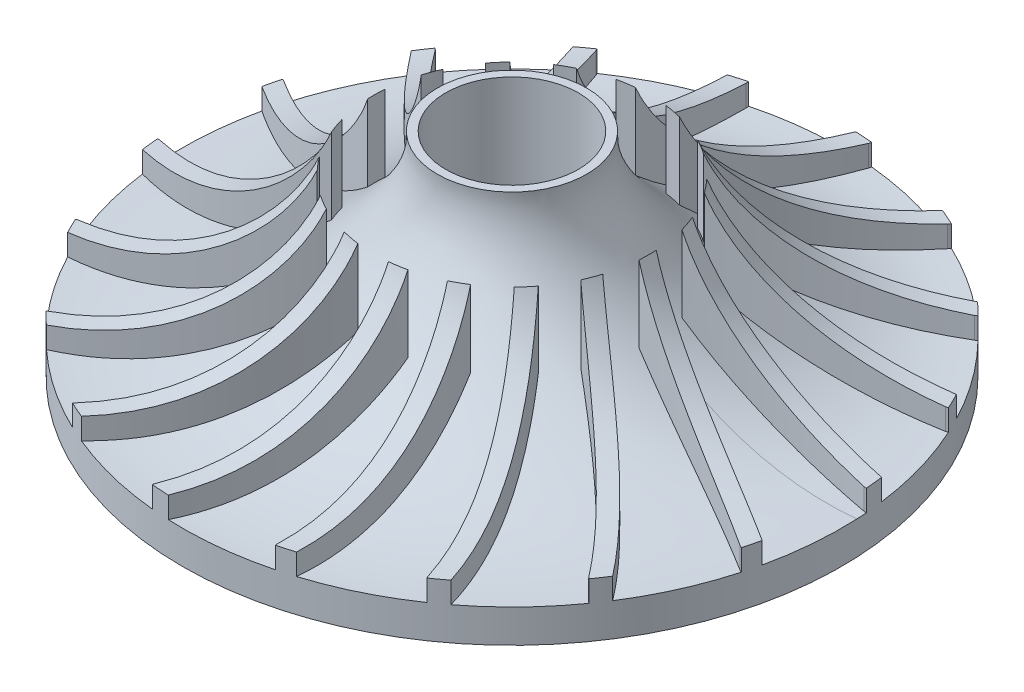
SolidWorks part; units mm, degrees
material "Aluminum Bronze"
ref_plane "Front Plane" through (0, 0, 0) normal (0, 0, 1) x (1, 0, 0)
ref_plane "Top Plane" through (0, 0, 0) normal (0, 1, 0) x (1, 0, 0)
ref_plane "Right Plane" through (0, 0, 0) normal (1, 0, 0) x (0, 0, -1)
curve "Shroud Curve"
curve "Impeller Curve"
curve "Blade Curve"
sketch "Sketch2" plane through (0, 0, 0) normal (0, 0, 1) x (1, 0, 0)
  line L0 (12.3936, 20.32) -> (31.524, 20.32)
  line L1 (31.524, 20.32) -> (31.524, 5.2084)
  spline S0 degree 3 poles (-987.5158, 25.9904) (14.3924, 25.4096) (12.3838, 22.8501) (12.394, 20.2062) (12.3983, 20.0433) (12.4153, 19.7646) (12.4464, 19.455) (12.5, 19.0868) (12.5725, 18.7015) (12.668, 18.288) (12.7893, 17.8459) (12.939, 17.3754) (13.1199, 16.8765) (13.3352, 16.3498) (13.5878, 15.7963) (13.8846, 15.2103) (14.2339, 14.5865) (14.6461, 13.9208) (15.1337, 13.2093) (15.7166, 12.4431) (16.4608, 11.5686) (17.3717, 10.6312) (18.3895, 9.7284) (19.3933, 8.9559) (20.3425, 8.3146) (21.265, 7.7651) (22.1833, 7.2836) (23.1089, 6.8589) (24.0463, 6.4862) (24.992, 6.1646) (25.9534, 5.89) (26.9392, 5.6596) (27.948, 5.4753) (28.9787, 5.3375) (30.0306, 5.2467) (30.8193, 5.2152) (31.2822, 5.2094) (31.3964, 5.2087) (31.4474, 5.2085) (36.9587, 5.195) (42.4601, 7.5368) (46.7066, -994.6744) knots -0.286221 -0.286221 -0.286221 -0.286221 0.000573 0.001147 0.01108 0.018892 0.032537 0.046055 0.060727 0.076613 0.093771 0.112259 0.132129 0.153434 0.17622 0.200532 0.227285 0.256591 0.288558 0.324244 0.364815 0.417623 0.471125 0.517692 0.559977 0.599882 0.638379 0.676541 0.714348 0.751783 0.788827 0.826738 0.865587 0.904104 0.943642 0.984281 0.992833 0.995696 0.997129 0.998564 1.615425 1.615425 1.615425 1.615425 only from (12.3936, 20.32) to (31.524, 5.2084) construction
  spline S1 degree 3 poles (12.3936, 20.32) (12.3936, 20.3149) (12.3937, 20.2945) (12.394, 20.2378) (12.396, 20.1285) (12.4051, 19.9045) (12.4293, 19.6044) (12.4765, 19.2357) (12.5395, 18.8663) (12.6241, 18.4693) (12.7311, 18.0501) (12.8642, 17.6027) (13.0263, 17.1273) (13.2201, 16.6241) (13.4517, 16.0871) (13.7253, 15.5171) (14.049, 14.9088) (14.4286, 14.2638) (14.8748, 13.5782) (15.4055, 12.8419) (16.0542, 12.0336) (16.9755, 11.0153) (18.0099, 10.0444) (19.1028, 9.1708) (20.0247, 8.5203) (20.9547, 7.9421) (21.8752, 7.4382) (22.7956, 6.9963) (23.7195, 6.61) (24.6625, 6.2706) (25.622, 5.9787) (26.6067, 5.7317) (27.6157, 5.5303) (28.6473, 5.3762) (29.7007, 5.2699) (30.5959, 5.2213) (31.1689, 5.2101) (31.3964, 5.2087) (31.4474, 5.2085) (31.4857, 5.2084) (31.5112, 5.2084) (31.524, 5.2084) knots 0 0 0 0 0.000573 0.002299 0.006366 0.012866 0.027514 0.040203 0.054662 0.069638 0.085834 0.103308 0.122113 0.142304 0.163927 0.187868 0.213381 0.24139 0.272007 0.305338 0.34342 0.38851 0.459669 0.502746 0.545774 0.586485 0.625835 0.66373 0.701259 0.738405 0.776386 0.814001 0.852529 0.892045 0.931258 0.971546 0.992833 0.995696 0.997129 0.998564 1 1 1 1
  point P4 (29.0733, 5.3935)
  point P6 (0, 0)
  point P8 (15.584, 20.3198)
ref_axis "Axis1" through (0, 21.336, 0) along (0, -1, 0)
revolve "Shroud" add sketch "Sketch2" angle 360 about axis through (0, 21.336, 0) along (0, -1, 0)
sketch "Sketch3" plane through (0, 0, 0) normal (0, 0, 1) x (1, 0, 0)
  line L0 (31.5224, 3.1749) -> (31.5224, 0)
  line L1 (31.5224, 0) -> (0, 0)
  line L2 (0, 0) -> (0, 20.32)
  line L3 (31.524, 20.32) -> (-31.524, 20.32) construction
  line L4 (7.1438, 20.3135) -> (0, 20.32)
  spline S7 degree 3 poles (-1987.4593, 163.9747) (15.0815, 23.5909) (7.237, 22.1997) (7.1404, 20.2633) (7.1388, 20.2349) (7.1374, 20.2066) (7.1335, 20.1218) (7.1286, 19.962) (7.1283, 19.6342) (7.1493, 19.2151) (7.2045, 18.7258) (7.2851, 18.2511) (7.3952, 17.7637) (7.5366, 17.2646) (7.7099, 16.7544) (7.9123, 16.2424) (8.1435, 15.7291) (8.4026, 15.2142) (8.6894, 14.6982) (9.0087, 14.1732) (9.361, 13.6396) (9.7473, 13.0984) (10.1682, 12.5501) (10.6246, 11.9955) (11.1243, 11.4283) (11.6762, 10.8425) (12.291, 10.2334) (12.9809, 9.5977) (13.7595, 8.9332) (14.6684, 8.2199) (15.8201, 7.4001) (17.0829, 6.6101) (18.3914, 5.8979) (19.5636, 5.3373) (20.7168, 4.8556) (21.8326, 4.4512) (22.9378, 4.1082) (24.0401, 3.8203) (25.1484, 3.5838) (26.273, 3.396) (27.4131, 3.2573) (28.5804, 3.1676) (29.775, 3.129) (30.6764, 3.1396) (31.2068, 3.16) (31.3443, 3.1662) (31.3995, 3.1688) (31.441, 3.1708) (37.6328, 3.4785) (43.5866, 8.1443) (152.6696, -1993.0178) knots -0.175256 -0.175256 -0.175256 -0.175256 0.000669 0.001536 0.002404 0.00327 0.004136 0.010183 0.017925 0.034167 0.04862 0.063032 0.07828 0.094393 0.110554 0.127643 0.144833 0.162141 0.180455 0.198922 0.218443 0.239045 0.259851 0.281779 0.304858 0.329116 0.35553 0.38416 0.415071 0.449318 0.490018 0.54459 0.585745 0.626499 0.663632 0.700247 0.735233 0.769651 0.80463 0.839062 0.874118 0.909854 0.946332 0.983621 0.992446 0.994976 0.996243 0.99751 0.998779 1.564382 1.564382 1.564382 1.564382 only from (7.1438, 20.3135) to (31.5224, 3.1749) construction
  spline S8 degree 3 poles (7.1438, 20.3135) (7.1431, 20.3062) (7.1417, 20.2895) (7.1404, 20.2633) (7.1388, 20.2349) (7.1374, 20.2066) (7.1335, 20.1218) (7.1286, 19.962) (7.1283, 19.6342) (7.1493, 19.2151) (7.2045, 18.7258) (7.2851, 18.2511) (7.3952, 17.7637) (7.5366, 17.2646) (7.7099, 16.7544) (7.9123, 16.2424) (8.1435, 15.7291) (8.4026, 15.2142) (8.6894, 14.6982) (9.0087, 14.1732) (9.361, 13.6396) (9.7473, 13.0984) (10.1682, 12.5501) (10.6246, 11.9955) (11.1243, 11.4283) (11.6762, 10.8425) (12.291, 10.2334) (12.9809, 9.5977) (13.7595, 8.9332) (14.6684, 8.2199) (15.8201, 7.4001) (17.0829, 6.6101) (18.3914, 5.8979) (19.5636, 5.3373) (20.7168, 4.8556) (21.8326, 4.4512) (22.9378, 4.1082) (24.0401, 3.8203) (25.1484, 3.5838) (26.273, 3.396) (27.4131, 3.2573) (28.5804, 3.1676) (29.775, 3.129) (30.6764, 3.1396) (31.2068, 3.16) (31.3443, 3.1662) (31.3995, 3.1688) (31.441, 3.1708) (31.4819, 3.1728) (31.5091, 3.1742) (31.5224, 3.1749) knots 0 0 0 0 0.000669 0.001536 0.002404 0.00327 0.004136 0.010183 0.017925 0.034167 0.04862 0.063032 0.07828 0.094393 0.110554 0.127643 0.144833 0.162141 0.180455 0.198922 0.218443 0.239045 0.259851 0.281779 0.304858 0.329116 0.35553 0.38416 0.415071 0.449318 0.490018 0.54459 0.585745 0.626499 0.663632 0.700247 0.735233 0.769651 0.80463 0.839062 0.874118 0.909854 0.946332 0.983621 0.992446 0.994976 0.996243 0.99751 0.998779 1 1 1 1
revolve "Impeller" add sketch "Sketch3" angle 360 about axis through (0, 21.336, 0) along (0, -1, 0)
sketch "Sketch6" plane through (0, 0, 0) normal (0, 1, 0) x (1, 0, 0)
  arc A1 (12.2144, -0.7732) -> (12.5729, 0.7732) centre (12.3936, 0) cw
  arc A2 (30.1522, -8.3254) -> (31.0078, -6.9882) centre (30.58, -7.6568) ccw
  arc A4 (30.376, -8.4239) -> (30.7718, -6.8379) centre (0, 0) ccw
  circle A6 centre (0, 0) radius 31.5224 construction
  arc A9 (13.1723, 0.631) -> (13.1496, -0.9982) centre (0, 0) cw
  circle A12 centre (0, 0) radius 12.3936 construction
  circle A13 centre (0, 0) radius 12.3936 construction
  spline S0 degree 3 poles (442.7335, 1953.011) (-2.4115, 1.5934) (5.2104, 1.6686) (12.9096, -0.1198) (14.0469, -0.3996) (15.8438, -0.8995) (18.1748, -1.6376) (20.7354, -2.5797) (23.4794, -3.756) (26.0506, -5.0115) (28.3794, -6.2947) (29.8541, -7.1939) (30.513, -7.6139) (30.5465, -7.6354) (36.7948, -11.6293) (42.0686, -17.1348) (1126.7136, 1665.009) knots -1.118742 -1.118742 -1.118742 -1.118742 0.001002 0.002004 0.077126 0.178187 0.284155 0.446993 0.590825 0.735722 0.879774 0.992981 0.996992 0.997995 0.998997 2.118966 2.118966 2.118966 2.118966 only from (12.3936, 0) to (30.58, -7.6568) construction
  spline S1 degree 3 poles (12.3936, 0) (12.4904, -0.0224) (12.6967, -0.0708) (13.1216, -0.1729) (13.8023, -0.3426) (14.8827, -0.6297) (16.8946, -1.2142) (19.41, -2.0688) (22.2719, -3.2199) (24.8527, -4.4069) (27.3913, -5.7302) (29.2525, -6.8202) (30.2839, -7.4679) (30.5241, -7.6211) (30.5576, -7.6425) (30.5744, -7.6532) (30.58, -7.6568) knots 0 0 0 0 0.015031 0.032062 0.066113 0.121166 0.201187 0.383066 0.522901 0.667756 0.812725 0.955894 0.993984 0.996992 0.998997 1 1 1 1
  spline S2 degree 1 poles (12.2144, -0.7732) (30.1522, -8.3254) knots 0 0 1 1 construction
  spline S3 degree 3 poles (12.2144, -0.7732) (12.4486, -0.8275) (12.8385, -0.9205) (14.4199, -1.315) (17.3224, -2.1524) (21.5335, -3.7174) (25.9586, -5.8069) (28.7797, -7.4473) (30.1522, -8.3254) knots 0 0 0 0 0.036883 0.061471 0.25 0.5 0.75 1 1 1 1
  spline S4 degree 1 poles (12.5729, 0.7732) (31.0078, -6.9882) knots 0 0 1 1 construction
  spline S5 degree 3 poles (12.5729, 0.7732) (12.7229, 0.7385) (12.9728, 0.6796) (14.6003, 0.2844) (17.6768, -0.59) (22.1503, -2.2525) (26.5926, -4.3502) (29.4354, -5.9917) (30.8506, -6.8878) (30.9489, -6.9505) (31.0078, -6.9882) knots 0 0 0 0 0.022988 0.038314 0.25 0.5 0.75 0.982599 0.989559 1 1 1 1
  point P11 (0, 0)
  point P12 (0, 0)
  dimension "D3" = 0.7937
  dimension "D1" = 0.7937
  dimension "D2" = 0.7937
sketch "Sketch5" plane through (0, 0, 0) normal (0, -1, 0) x (1, 0, 0)
  circle A0 centre (0, 0) radius 6.35
  dimension "D1" = 12.7
extrude "Shaft Hole" cut sketch "Sketch5" against normal through all
extrude "Boss-Extrude2" add sketch "Sketch6" along normal through all contours S5 A1 A9 S1 A4 | A9 S3 A2 A4 S1 region at (22.0258, 0, 3.8518) region at (22.1341, 0, 3.036)
pattern_circular "CirPattern1" count 18 over 360 about axis through (0, 21.336, 0) along (0, -1, 0) of "Boss-Extrude2"
revolve "Cut-Revolve1" cut sketch "Sketch2<3>" angle 360 about axis through (0, 21.336, 0) along (0, -1, 0)
sketch "Sketch2<3>" plane through (0, 0, 0) normal (0, 0, 1) x (1, 0, 0) same geometry as "Sketch2"
